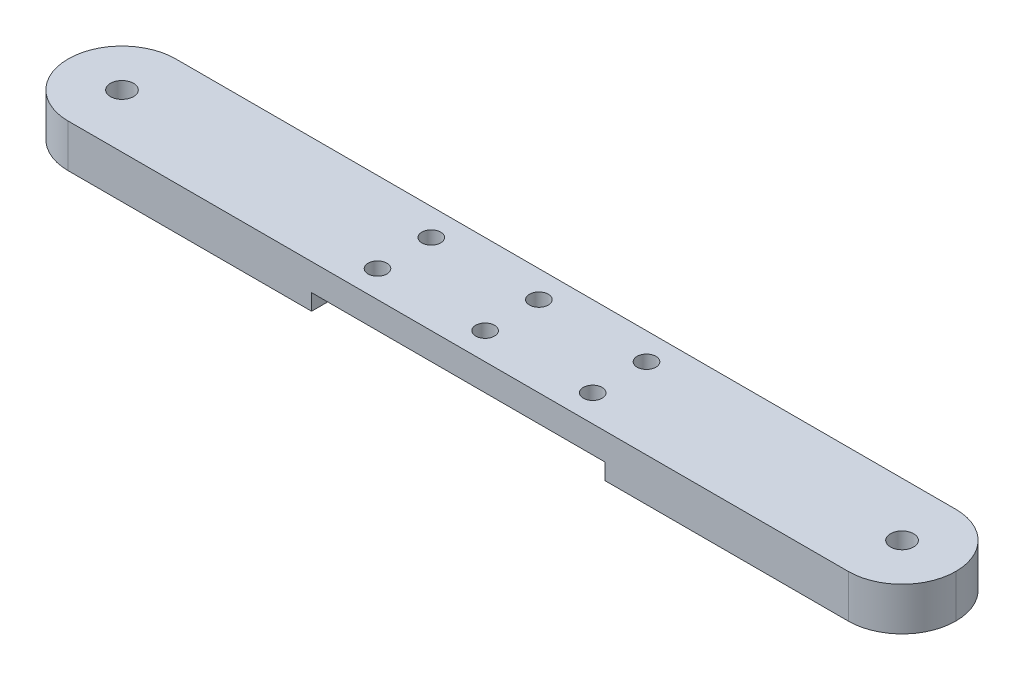
SolidWorks part; units mm, degrees
ref_plane "정면" through (0, 0, 0) normal (0, 0, 1) x (1, 0, 0)
ref_plane "윗면" through (0, 0, 0) normal (0, 1, 0) x (1, 0, 0)
ref_plane "우측면" through (0, 0, 0) normal (1, 0, 0) x (0, 0, -1)
sketch "스케치1" plane through (0, 0, 0) normal (0, 0, 1) x (1, 0, 0)
  line L0 (28, -2.5) -> (83.25, -2.5)
  line L1 (-81.75, 5.5) -> (83.25, 5.5)
  line L2 (-81.75, 5.5) -> (-81.75, -2.5)
  line L3 (-81.75, -2.5) -> (-26.5, -2.5)
  line L4 (83.25, 5.5) -> (83.25, -2.5)
  line L8 (-26.5, -2.5) -> (-26.5, 0.5)
  line L9 (-26.5, 0.5) -> (28, 0.5)
  line L10 (28, -2.5) -> (28, 0.5)
  point P0 (0, 0)
  point P6 (0, -2.5)
  dimension "D1" = 165
  dimension "D2" = 54.5
  dimension "D3" = 8
  dimension "D4" = 3
extrude "보스-돌출1" add sketch "스케치1" along normal blind 20
sketch "스케치2" plane through (0, 5.5, 0) normal (0, 1, 0) x (1, 0, 0)
  line L0 (-81.75, -10) -> (83.25, -10) construction
  line L1 (-81.75, -20) -> (-81.75, 0) construction
  line L2 (83.25, -20) -> (83.25, 0) construction
  line L6 (-19.25, -15) -> (20.75, -15) construction
  line L7 (-19.25, -15) -> (-19.25, -5) construction
  line L8 (-19.25, -5) -> (20.75, -5) construction
  line L9 (20.75, -15) -> (20.75, -5) construction
  line L10 (-19.25, -15) -> (20.75, -5) construction
  line L11 (-19.25, -5) -> (20.75, -15) construction
  circle A0 centre (-71.75, -10) radius 2.15
  circle A1 centre (73.25, -10) radius 2.15
  circle A2 centre (-19.25, -5) radius 1.75
  circle A3 centre (0.75, -5) radius 1.75
  circle A4 centre (20.75, -5) radius 1.75
  circle A5 centre (20.75, -15) radius 1.75
  circle A6 centre (0.75, -15) radius 1.75
  circle A7 centre (-19.25, -15) radius 1.75
  point P10 (0.75, -10)
  dimension "D1" = 4.3
  dimension "D2" = 4.3
  dimension "D3" = 10
  dimension "D4" = 10
  dimension "D7" = 3.5
  dimension "D5" = 40
  dimension "D6" = 10
extrude "컷-돌출1" cut sketch "스케치2" against normal blind 20
fillet "필렛1" radius 10 4 edges at (83.25, 1.5, 0) (83.25, 1.5, 20) (-81.75, 1.5, 0) (-81.75, 1.5, 20)
